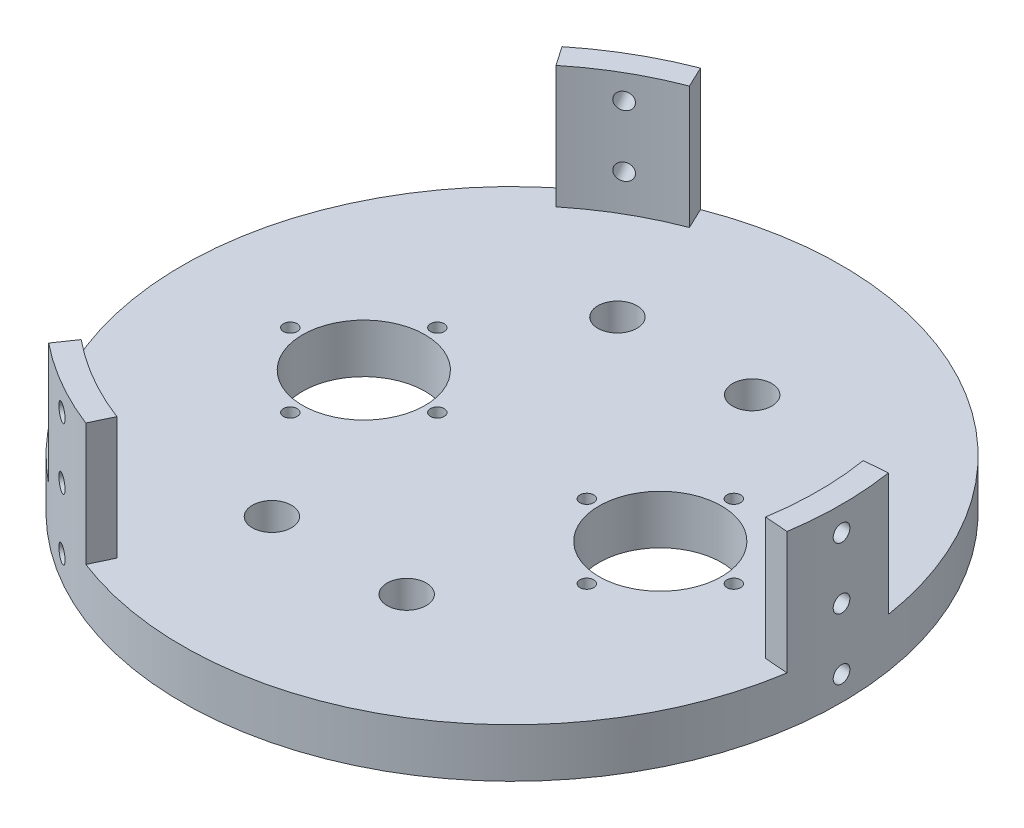
SolidWorks part; units mm, degrees
material "6061-T6 (SS)"
ref_plane "Front" through (0, 0, 0) normal (0, 0, 1) x (1, 0, 0)
ref_plane "Top" through (0, 0, 0) normal (0, 1, 0) x (1, 0, 0)
ref_plane "Right" through (0, 0, 0) normal (1, 0, 0) x (0, 0, -1)
sketch "Sketch1" plane through (0, 0, 0) normal (0, 1, 0) x (1, 0, 0)
  line L1 (0, 0) -> (127.635, 0)
  line L2 (0, 0) -> (0, 127.635)
  line L3 (0, 127.635) -> (127.635, 127.635)
  line L4 (127.635, 0) -> (127.635, 127.635)
  dimension "D1" = 127.635
  dimension "D2" = 127.635
extrude "Main Plate" add sketch "Sketch1" along normal blind 12.7
sketch "Sketch9" plane through (0, 12.7, 0) normal (0, 1, 0) x (1, 0, 0)
  circle A0 centre (63.8175, 63.8175) radius 85.725
  dimension "D1" = 171.45
extrude "Boss-Extrude1" add sketch "Sketch9" against normal up to surface (12.7 mm away) contours A0 up to face at (63.8175, 0, -63.8175)
sketch "Sketch10" plane through (0, 12.7, 0) normal (0, 1, 0) x (1, 0, 0)
  circle A0 centre (63.8175, 63.8175) radius 95.25
  circle A1 centre (63.8175, 63.8175) radius 85.4075
  dimension "D1" = 170.815
  dimension "D2" = 190.5
extrude "Cut-Extrude1" cut sketch "Sketch10" against normal blind 167.64 contours A0 | A1
sketch "Sketch14" plane through (0, 12.7, 0) normal (0, 1, 0) x (1, 0, 0)
  line L0 (201.1692, 63.8175) -> (-73.4523, 63.8175) construction
ref_plane "Plane1" through (0, 0, -63.8175) normal (0, 0, -1) x (-1, 0, 0)
ref_plane "Plane3" through (0, 6.35, 0) normal (0, 1, 0) x (1, 0, 0)
ref_plane "Plane2" through (-21.59, 0, 0) normal (-1, 0, 0) x (0, 0, 1)
sketch "Sketch18" plane through (0, 6.35, 0) normal (0, 1, 0) x (1, 0, 0)
  circle A0 centre (63.8175, 63.8175) radius 85.4075
  circle A1 centre (63.8175, 63.8175) radius 79.375
  circle A4 centre (63.8175, 63.8175) radius 85.4075 construction
  dimension "D1" = 158.75
extrude "Boss-Extrude2" add sketch "Sketch18" along normal blind 38.1
sketch "Sketch20" plane through (0, 12.7, 0) normal (0, 1, 0) x (1, 0, 0)
  line L0 (63.8175, 143.1925) -> (63.8175, -15.5575) construction
  line L1 (-15.5575, 63.8175) -> (143.1925, 63.8175) construction
  line L2 (63.8175, 63.8175) -> (-15.5575, -73.664) construction
  circle A0 centre (63.8175, 63.8175) radius 79.375 construction
  dimension "D1" = 30
ref_plane "Plane5" through (-15.5575, 12.7, 73.664) normal (-0.5, 0, 0.866) x (0.866, 0, 0.5)
sketch "Sketch15" plane through (166.2216, 0, 178.6143) normal (0.5, 0, -0.866) x (-0.866, 0, -0.5)
  line L3 (289.2754, 44.45) -> (130.5254, 44.45) construction
  line L4 (124.4929, 0) -> (295.3079, 0) construction
  line L6 (278.6412, 12.7) -> (141.1597, 12.7) construction
  circle A0 centre (209.9004, 22.225) radius 2.159
  circle A1 centre (209.9004, 38.1) radius 2.159
  circle A2 centre (209.9004, 6.35) radius 2.159
  point P16 (209.9004, 12.7)
  dimension "D1" = 4.318
  dimension "D2" = 15.875
  dimension "D3" = 4.318
  dimension "D4" = 4.318
  dimension "D5" = 6.35
  dimension "D6" = 6.35
  dimension "D7" = 0
extrude "Cut-Extrude3" cut sketch "Sketch15" along normal blind 88.9
pattern_circular "CirPattern1" count 3 over 360 about axis through (63.8175, -154.94, -63.8175) along (0, 1, 0) of "Cut-Extrude3" reverse direction yes
ref_plane "Plane4" through (63.8175, 0, 0) normal (-1, 0, 0) x (0, 0, 1)
sketch "Sketch21" plane through (0, 12.7, 0) normal (0, 1, 0) x (1, 0, 0)
  line L1 (-15.5575, 63.8175) -> (143.1925, 63.8175) construction
  line L2 (102.235, 63.8175) -> (102.235, 100.651) construction
  line L3 (63.8175, 87.3125) -> (63.8175, -87.3125) construction
  circle A0 centre (102.235, 63.8175) radius 15.875
  circle A1 centre (102.235, 82.8675) radius 1.778
  circle A2 centre (25.4, 63.8175) radius 15.875
  circle A3 centre (121.285, 63.8175) radius 1.778
  circle A4 centre (102.235, 44.7675) radius 1.778
  circle A5 centre (83.185, 63.8175) radius 1.778
  circle A6 centre (25.4, 82.8675) radius 1.778
  circle A7 centre (6.35, 63.8175) radius 1.778
  circle A8 centre (25.4, 44.7675) radius 1.778
  circle A9 centre (44.45, 63.8175) radius 1.778
  dimension "D1" = 31.75
  dimension "D2" = 3.556
  dimension "D6" = 19.05
  dimension "D3" = 19.05
  dimension "D4" = 76.835
  dimension "D7" = 19.05
  dimension "D5" = 4
extrude "CO2 Mounts" cut sketch "Sketch21" against normal through all
sketch "Sketch22" plane through (0, 12.7, 0) normal (0, 1, 0) x (1, 0, 0)
  line L0 (63.8175, 87.3125) -> (63.8175, -87.3125) construction
  line L1 (87.3125, 63.8175) -> (-87.3125, 63.8175) construction
  circle A0 centre (46.355, 108.585) radius 5.08
  circle A1 centre (81.28, 108.585) radius 5.08
  circle A2 centre (81.28, 19.05) radius 5.08
  circle A3 centre (46.355, 19.05) radius 5.08
  dimension "D1" = 10.16
  dimension "D2" = 34.925
  dimension "D3" = 89.535
extrude "Cut-Extrude5" cut sketch "Sketch22" against normal through all
sketch "Sketch23" plane through (0, 12.7, 0) normal (0, 1, 0) x (1, 0, 0)
  line L0 (13.6787, 125.352) -> (7.5523, 134.2379)
  line L1 (15.1867, 11.8815) -> (13.6787, 2.283) construction
  line L3 (-15.5575, 63.8175) -> (143.1925, 63.8175) construction
  line L4 (63.8175, 143.1925) -> (63.8175, -15.5575) construction
  line L5 (-15.5575, 63.8175) -> (143.1925, 63.8175)
  line L6 (63.8175, 143.1925) -> (63.8175, -15.5575)
  line L7 (13.6787, 2.283) -> (6.9592, -7.4631)
  line L8 (-19.2671, 125.3206) -> (-48.797, 60.3978)
  line L9 (-48.797, 60.3978) -> (-9.8843, 7.0525)
  line L10 (-9.8843, 7.0525) -> (6.9592, -7.4631)
  line L11 (24.1345, -4.9259) -> (13.6787, 2.283) construction
  line L14 (7.5523, 134.2379) -> (-19.2671, 125.3206)
  line L15 (24.1345, 132.5609) -> (13.6787, 125.352) construction
  line L28 (63.8175, 63.8175) -> (24.1345, -4.9259) construction
  line L29 (63.8175, 63.8175) -> (24.1345, 132.5609) construction
  line L30 (142.1773, 76.4717) -> (152.9359, 77.3344)
  line L31 (152.9359, 77.3344) -> (158.6231, 105.0193)
  line L32 (158.6231, 105.0193) -> (117.1632, 163.0543)
  line L33 (117.1632, 163.0543) -> (51.5085, 156.0277)
  line L34 (51.5085, 156.0277) -> (30.5159, 148.6985)
  line L35 (35.5964, 138.0062) -> (30.5159, 148.6985)
  line L36 (35.5964, -10.3712) -> (30.9643, -20.1198)
  line L37 (30.9643, -20.1198) -> (52.0965, -38.8874)
  line L38 (52.0965, -38.8874) -> (123.0863, -31.9996)
  line L39 (123.0863, -31.9996) -> (149.8284, 28.3723)
  line L40 (149.8284, 28.3723) -> (153.9775, 50.217)
  line L41 (142.1773, 51.1633) -> (153.9775, 50.217)
  circle A0 centre (63.8175, 63.8175) radius 79.375 construction
  arc A1 (13.6787, 2.283) -> (13.6787, 125.352) centre (63.8175, 63.8175) cw
  circle A3 centre (63.8175, 63.8175) radius 79.375
  arc A6 (35.5964, 138.0062) -> (142.1773, 76.4717) centre (63.8175, 63.8175) cw
  arc A7 (142.1773, 51.1633) -> (35.5964, -10.3712) centre (63.8175, 63.8175) cw
  circle A9 centre (63.8175, 63.8175) radius 79.375
  circle M15 centre (63.8175, 63.8175) radius 79.375
  dimension "D1" = 79.375
  dimension "D2" = 0
  dimension "D3" = 12.7
  dimension "D4" = 90
  dimension "D5" = 12.7
  dimension "D6" = 90
  dimension "D8" = 60.004
  dimension "D9" = 60.004
  dimension "D7" = 3
extrude "Cut-Extrude6" cut sketch "Sketch23" along normal blind 111.6 contours L9 L10 L7 L8 M15 | L34 L35 A6 L30 L31 L32 L33 | L40 L41 A7 L36 L37 L38 L39 region at (-18.2379, 12.7, -69.3048)
